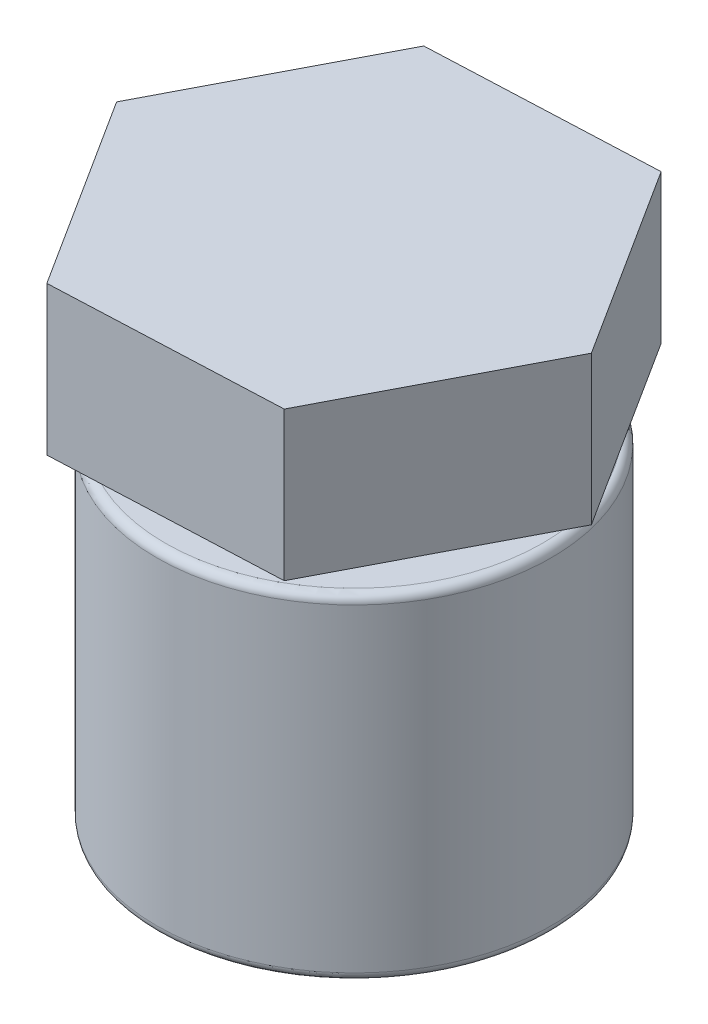
SolidWorks part; units mm, degrees
ref_plane "Front Plane" through (0, 0, 0) normal (0, 0, 1) x (1, 0, 0)
ref_plane "Top Plane" through (0, 0, 0) normal (0, 1, 0) x (1, 0, 0)
ref_plane "Right Plane" through (0, 0, 0) normal (1, 0, 0) x (0, 0, -1)
sketch "Sketch1" plane through (0, 0, 0) normal (0, 0, 1) x (1, 0, 0)
  line L0 (0, 51.3092) -> (9.366, 51.3092)
  line L1 (9.366, 51.3092) -> (9.366, 43.1649)
  line L2 (9.366, 43.1649) -> (14.2525, 43.1649)
  line L3 (14.2525, 43.1649) -> (14.2525, 29.9433)
  line L4 (14.2525, 29.9433) -> (14.897, 29.9433)
  line L5 (14.897, 29.9433) -> (14.897, 28.9123)
  line L6 (14.897, 28.9123) -> (14.2525, 28.9123)
  line L7 (14.2525, 28.9123) -> (14.2525, 22.8041)
  line L8 (14.2525, 22.8041) -> (46.4226, 22.8041)
  line L9 (46.4226, 22.8041) -> (46.4226, -56.1958)
  line L10 (46.4226, -56.1958) -> (0, -56.1958)
  line L11 (0, -56.1958) -> (0, -43.9793)
  line L12 (0, -43.9793) -> (42.3504, -43.9793)
  line L13 (42.3504, -43.9793) -> (42.3504, 17.5103)
  line L14 (42.3504, 17.5103) -> (0, 17.5103)
  line L15 (0, 17.5103) -> (0, 51.3092)
revolve "Revolve1" add sketch "Sketch1" angle 360 about L15
fillet "Fillet1" radius 2 2 edges at (0, -56.1958, -46.4226) (0, 22.8041, -46.4226)
sketch "Sketch2" plane through (0, 29.9433, 0) normal (0, 1, 0) x (1, 0, 0)
  line L1 (28.7907, -45.2162) -> (53.5537, 2.3254)
  line L2 (53.5537, 2.3254) -> (24.763, 47.5416)
  line L3 (24.763, 47.5416) -> (-28.7907, 45.2162)
  line L4 (-28.7907, 45.2162) -> (-53.5537, -2.3254)
  line L5 (-53.5537, -2.3254) -> (-24.763, -47.5416)
  line L6 (-24.763, -47.5416) -> (28.7907, -45.2162)
  circle A0 centre (0, 0) radius 46.4226 construction
  circle A1 centre (0, 0) radius 46.4226 construction
extrude "Boss-Extrude1" add sketch "Sketch2" along normal blind 35 separate body
revolve "Cut-Revolve1" cut sketch "Sketch1<2>" angle 360 about L15
sketch "Sketch1<2>" plane through (0, 0, 0) normal (0, 0, 1) x (1, 0, 0) same geometry as "Sketch1"
